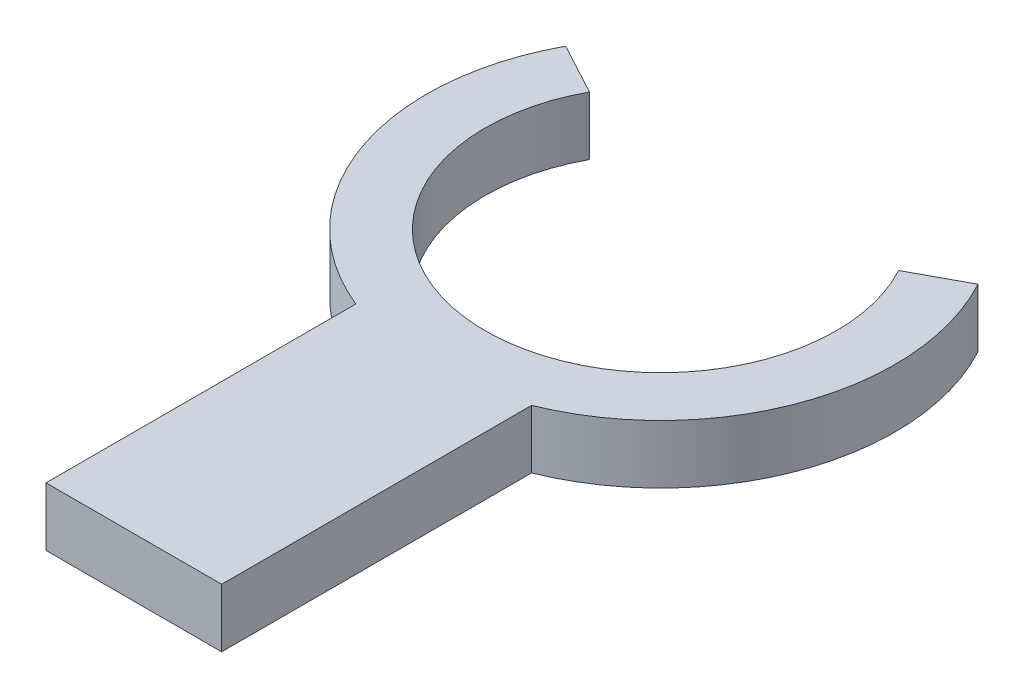
SolidWorks part; units mm, degrees
ref_plane "Front Plane" through (0, 0, 0) normal (0, 0, 1) x (1, 0, 0)
ref_plane "Top Plane" through (0, 0, 0) normal (0, 1, 0) x (1, 0, 0)
ref_plane "Right Plane" through (0, 0, 0) normal (1, 0, 0) x (0, 0, -1)
sketch "Sketch1" plane through (0, 0, 0) normal (0, 1, 0) x (1, 0, 0)
  line L0 (-40, 0) -> (-30, 0)
  line L1 (-30, 0) -> (30, 0)
  line L2 (30, 0) -> (40, 0)
  line L3 (0, 0) -> (0, -90) construction
  line L4 (-15, -90) -> (15, -90) construction
  line L5 (-15, -90) -> (15, -90)
  line L6 (-15, -90) -> (-14.9891, 0)
  line L7 (15, -90) -> (15.0109, 0)
  line L8 (-14.9891, 0) -> (15.0109, 0)
  line L9 (0, 0) -> (-35.214, 18.9731)
  line L10 (0, 0) -> (35.214, 18.9731)
  circle A0 centre (0, 0) radius 30
  circle A1 centre (0, 0) radius 40
  point P12 (0, -90)
  dimension "D1" = 60
  dimension "D2" = 80
  dimension "D3" = 90
  dimension "D4" = 30
extrude "Boss-Extrude1" add sketch "Sketch1" along normal blind 10 contours L9 A1 L0 A0 | L0 A1 L6 A0 | L6 A1 L7 A0 | A1 L6 L5 L7 | L7 A1 L2 A0 | L2 A1 L10 A0 region at (-33.8211, 0, -8.5315) region at (-28.2512, 0, 17.952) region at (0.0033, 0, 64.5135) region at (0.0076, 0, 33.8383) region at (33.8211, 0, -8.5315) region at (28.2565, 0, 17.9467)
